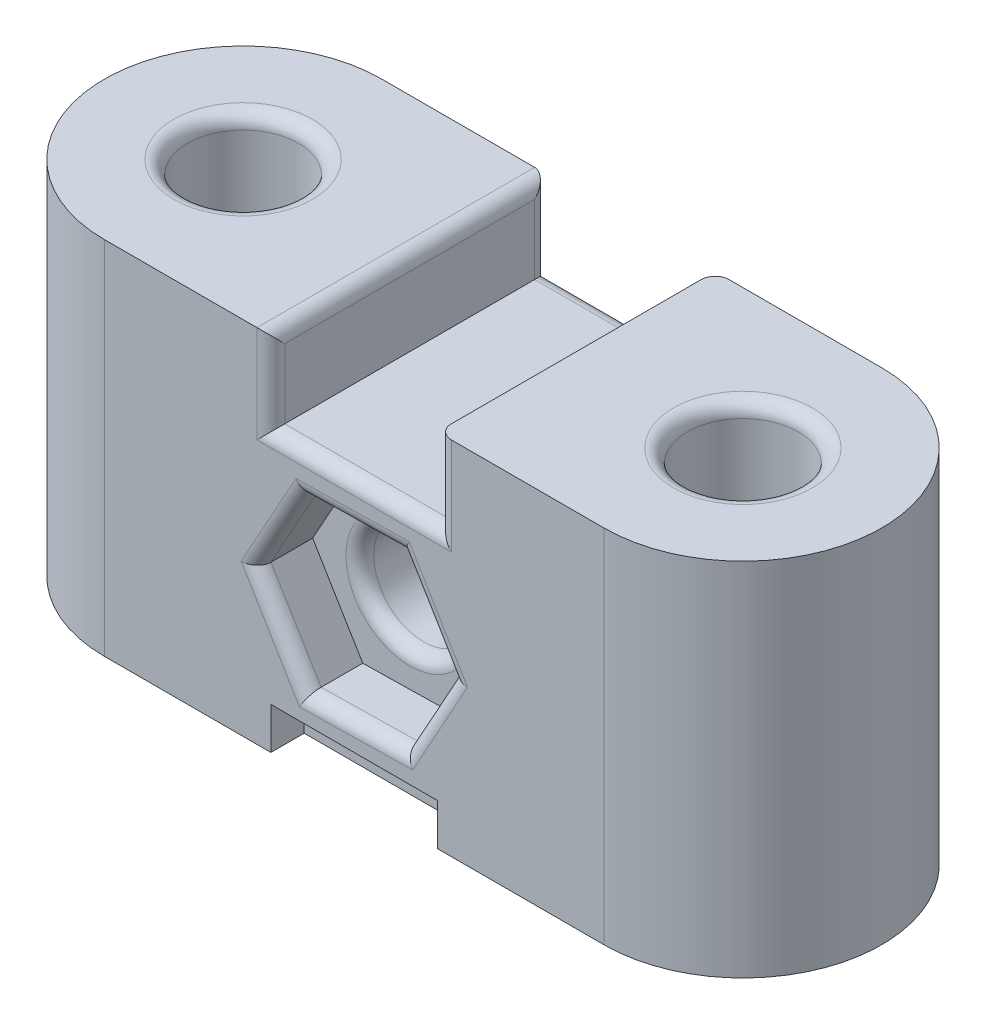
SolidWorks part; units mm, degrees
ref_plane "Front Plane" through (0, 0, 0) normal (0, 0, 1) x (1, 0, 0)
ref_plane "Top Plane" through (0, 0, 0) normal (0, 1, 0) x (1, 0, 0)
ref_plane "Right Plane" through (0, 0, 0) normal (1, 0, 0) x (0, 0, -1)
sketch "Belt Clamp" plane through (0, 0, 0) normal (0, 1, 0) x (1, 0, 0)
  line L1 (-18, 10) -> (0, 10)
  line L3 (-18, 0) -> (0, 0)
  arc A0 (-18, 10) -> (-18, 0) centre (-18, 5) ccw
  arc A1 (0, 0) -> (0, 10) centre (0, 5) ccw
  dimension "D1" = 18
  dimension "D2" = 10
extrude "Boss-Extrude2" add sketch "Belt Clamp" along normal blind 13
sketch "Screw Holes" plane through (0, 0, 0) normal (0, -1, 0) x (1, 0, 0)
  circle A0 centre (0, -5) radius 2
  circle A1 centre (-18, -5) radius 2
  dimension "D1" = 4
extrude "Cut-Extrude1" cut sketch "Screw Holes" against normal up to surface (13 mm away) up to face at (-9, 13, -5)
fillet "Fillet1" radius 0.5 4 edges at (0, 13, -3) (-18, 13, -3) (0, 0, -7) (-18, 0, -7)
sketch "Belt Opening" plane through (0, 13, 0) normal (0, 1, 0) x (1, 0, 0)
  line L2 (5, 5) -> (-23, 5) construction
  line L3 (-9, 0) -> (-9, 10) construction
  line L4 (-18, 0) -> (0, 0) construction
  line L5 (0, 10) -> (-18, 10) construction
  line L8 (-6, 0) -> (-12, 0)
  line L9 (-6, 0) -> (-6, 10)
  line L10 (-6, 10) -> (-12, 10)
  line L11 (-12, 0) -> (-12, 10)
  line L12 (-6, 0) -> (-12, 10) construction
  line L13 (-6, 10) -> (-12, 0) construction
  arc A0 (0, 0) -> (0, 10) centre (0, 5) ccw construction
  arc A1 (-18, 10) -> (-18, 0) centre (-18, 5) ccw construction
  point P15 (-9, 5)
  dimension "D1" = 6
extrude "Cut-Extrude2" cut sketch "Belt Opening" against normal blind 3
sketch "Hex Nut" plane through (0, 0, 0) normal (0, 0, 1) x (1, 0, 0)
  line L0 (-12, 10) -> (-6, 10) construction
  line L4 (-12.495, 5.4372) -> (-5.4961, 5.5628) construction
  line L6 (-9.0499, 8.5306) -> (-8.9412, 2.4694) construction
  line L12 (-12.495, 5.4372) -> (-10.6909, 2.438)
  line L13 (-10.6909, 2.438) -> (-7.1915, 2.5008)
  line L14 (-7.1915, 2.5008) -> (-5.4961, 5.5628)
  line L15 (-5.4961, 5.5628) -> (-7.3002, 8.562)
  line L16 (-7.3002, 8.562) -> (-10.7997, 8.4992)
  line L17 (-10.7997, 8.4992) -> (-12.495, 5.4372)
  circle A0 centre (-8.9956, 5.5) radius 3.0311 construction
  point P0 (-9, 10)
  dimension "D1" = 7
  dimension "D2" = 4.5
extrude "Cut-Extrude3" cut sketch "Hex Nut" against normal blind 2
sketch "Stretcher Hole" plane through (0, 0, -2) normal (0, 0, 1) x (1, 0, 0)
  line L1 (-9.0499, 8.5306) -> (-8.9412, 2.4694) construction
  line L2 (-7.3002, 8.562) -> (-10.7997, 8.4992) construction
  line L3 (-10.6909, 2.438) -> (-7.1915, 2.5008) construction
  circle A0 centre (-8.9956, 5.5) radius 1.8
  dimension "D1" = 3.6
extrude "Cut-Extrude4" cut sketch "Stretcher Hole" against normal up to surface (8 mm away) up to face at (-9, 9, -10)
fillet "Fillet2" radius 0.5 2 edges at (-7.1956, 5.5, -2) (-7.1956, 5.5, -10)
fillet "Fillet3" radius 0.5 6 edges at (-6.3438, 4.0318, 0) (-6.3982, 7.0624, 0) (-9.0499, 8.5306, 0) (-11.6473, 6.9682, 0) (-11.5929, 3.9376, 0) (-8.9412, 2.4694, 0)
fillet "Fillet8" radius 0.5 6 edges at (-12, 11.5, 0) (-6, 11.5, 0) (-12, 13, -5) (-12, 11.5, -10) (-9, 10, -10) (-6, 11.5, -10)
fillet "Fillet9" radius 0.5 1 edges at (-9, 10, 0)
sketch "Sketch1" plane through (0, 0, 0) normal (0, -1, 0) x (1, 0, 0)
  line L0 (-9, -10) -> (-9, 0) construction
  line L1 (0, -10) -> (-18, -10) construction
  line L2 (-18, 0) -> (0, 0) construction
  line L4 (-6, 1.2) -> (-12, 1.2)
  line L5 (-6, 1.2) -> (-6, -1.2)
  line L6 (-6, -1.2) -> (-12, -1.2)
  line L7 (-12, 1.2) -> (-12, -1.2)
  line L8 (-6, 1.2) -> (-12, -1.2) construction
  line L9 (-6, -1.2) -> (-12, 1.2) construction
  line L10 (-6, -3.7) -> (-12, -3.7)
  line L11 (-6, -3.7) -> (-6, -6.3)
  line L12 (-6, -6.3) -> (-12, -6.3)
  line L13 (-12, -3.7) -> (-12, -6.3)
  line L14 (-6, -3.7) -> (-12, -6.3) construction
  line L15 (-6, -6.3) -> (-12, -3.7) construction
  line L16 (-6, -11.2) -> (-12, -11.2)
  line L17 (-6, -11.2) -> (-6, -8.8)
  line L18 (-6, -8.8) -> (-12, -8.8)
  line L19 (-12, -11.2) -> (-12, -8.8)
  line L20 (-6, -11.2) -> (-12, -8.8) construction
  line L21 (-6, -8.8) -> (-12, -11.2) construction
  point P10 (-9, -5)
  dimension "D1" = 6
  dimension "D2" = 2.4
  dimension "D3" = 2.5
  dimension "D5" = 2.5
extrude "Cut-Extrude5" cut sketch "Sketch1" against normal blind 1.5
